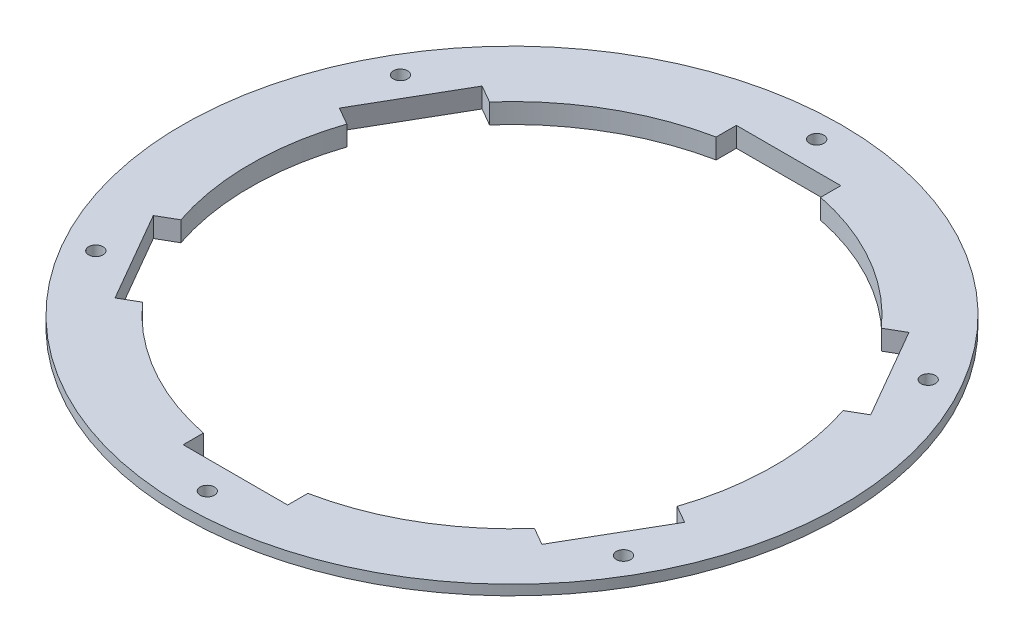
SolidWorks part; units mm, degrees
material "6061 Alloy"
ref_plane "Front Plane" through (0, 0, 0) normal (0, 0, 1) x (1, 0, 0)
ref_plane "Top Plane" through (0, 0, 0) normal (0, 1, 0) x (1, 0, 0)
ref_plane "Right Plane" through (0, 0, 0) normal (1, 0, 0) x (0, 0, -1)
sketch "Sketch1" plane through (0, 0, 0) normal (0, 1, 0) x (1, 0, 0)
  line L0 (-13.335, -65.4575) -> (-13.335, -69.3414)
  line L1 (13.335, -65.4575) -> (13.335, -69.3414)
  line L2 (-13.335, -70.612) -> (13.335, -70.612)
  line L3 (13.335, -69.3414) -> (13.335, -70.612)
  line L4 (-13.335, -69.3414) -> (-13.335, -70.612)
  circle A0 centre (0, 0) radius 66.802
  circle A1 centre (0, 0) radius 84.1375
  circle A2 centre (0, 0) radius 70.612
  circle A3 centre (0, -77.7875) radius 1.8288
  point P14 (0, 0)
  dimension "D1" = 133.604
  dimension "D2" = 168.275
  dimension "D8" = 3.6576
  dimension "D4" = 13.335
  dimension "D5" = 13.335
  dimension "D7" = 77.7875
  dimension "D3" = 3.81
extrude "Boss-Extrude1" add sketch "Sketch1" along normal blind 5.08 contours L1 A2 L0 A0 | A1 A2 A0 region at (-15.3232, 0, 67.3995) region at (-81.7577, 0, 0)
pattern_circular "CirPattern1" count 6 over 360 about axis through (0, 5.08, 0) along (0, 1, 0) of face at (-13.335, 2.54, 68.0348) of face at (13.335, 2.54, 68.0348) of face at (0, 5.08, 79.6163) of face at (0, 2.54, 70.612)
sketch "Sketch2" plane through (0, 0, 0) normal (1, 0, 0) x (0, 0, -1)
  line L0 (84.1375, 5.08) -> (-84.1375, 5.08) construction
  line L1 (-84.1375, 0) -> (84.1375, 0) construction
  line L2 (84.1375, 5.08) -> (-84.1375, 5.08)
  line L3 (-84.1375, 0) -> (84.1375, 0)
  line L4 (0, 0) -> (0, 5.08) construction
  circle A0 centre (-83.2231, 0) radius 2.667
  dimension "D1" = 5.334
  dimension "D2" = 0.9144
revolve "Cut-Revolve1" cut sketch "Sketch2" angle 360 about L4 region at (0, 0, 85.8147)
sketch "Sketch4" plane through (0, 0, 0) normal (0, -1, 0) x (1, 0, 0)
  line L0 (0, 0) -> (36.9888, -64.0664) construction
  line L1 (0, 0) -> (0, -39.7137) construction
  circle A0 centre (36.9888, -64.0664) radius 5.588
  circle M34 centre (0, 0) radius 80.5561
  dimension "D2" = 11.176
  dimension "D1" = 73.9775
  dimension "D3" = 30
extrude "Cut-Extrude1" cut sketch "Sketch4" against normal blind 1.905 contours A0 M34 region at (36.9888, 0, -64.0664)
pattern_circular "CirPattern2" count 3 over 360 about axis through (0, 0, 0) along (0, 1, 0) of "Cut-Extrude1"
equation "\"Middle Coupler Inner Daimeter\"= 4.75in"
equation "\"Middle Coupler  Wall Thickness\" = 0.25in"
equation "\"Middle Coupler Bottom Thickness\"= 0.2in"
equation "\"Bearing Rail Offset\"= 0.45in"
equation "\"3-56 UNF Tap\"= 0.089in"
equation "\"3-56 UNF Clearance\"= 0.104in"
equation "\"Ball Bearing Distance\"= 0.03in"
equation "\"D1@Sketch1\"=\"Middle Coupler Inner Daimeter\"+0.5+0.005*2in"
equation "\"TCA Outer Diameter\" = 6.625in"
equation "\"D2@Sketch1\"=\"TCA Outer Diameter\""
equation "\"D4@Sketch1\"=0.50 + (0.05/2)"
equation "\"D5@Sketch1\"=\"D4@Sketch1\""
equation "\"D7@Sketch1\"=(\"D2@Sketch1\"-0.5)/2"
equation "\"D8@Sketch1\"=\"6-32 Clearance\""
equation "\"D2@Sketch2\"=\"Interstage Aeroframe Wall Thickness\"/2"
equation "\"Interstage Aeroframe Wall Thickness\" = 0.072in"
equation "\"D1@Sketch4\"=((\"Middle Coupler Inner Daimeter\"+0.625in)/2in+0.225in)"
equation "\"Compression Spring OD\"= 0.42in"
equation "\"10-24 Tap\"= 0.157in"
equation "\"10-24 Clearance\"= 0.196in"
equation "\"D2@Sketch4\"=\"Compression Spring OD\"+0.02"
equation "\"D3@Sketch1\"=0.125in+(0.05/2)"
equation "\"Lower Stage Fuselage Wall Thickness\" = 0.25in"
equation "\"6-32 Tap\" = 0.107in"
equation "\"1/4-20 Tap\" = 0.201in"
equation "\"3-48 Tap\"= 0.079in"
equation "\"12-24 Tap\" = 0.177in"
equation "\"3-48 Clearance\" = 0.104in"
equation "\"6-32 Clearance\" = 0.144"
